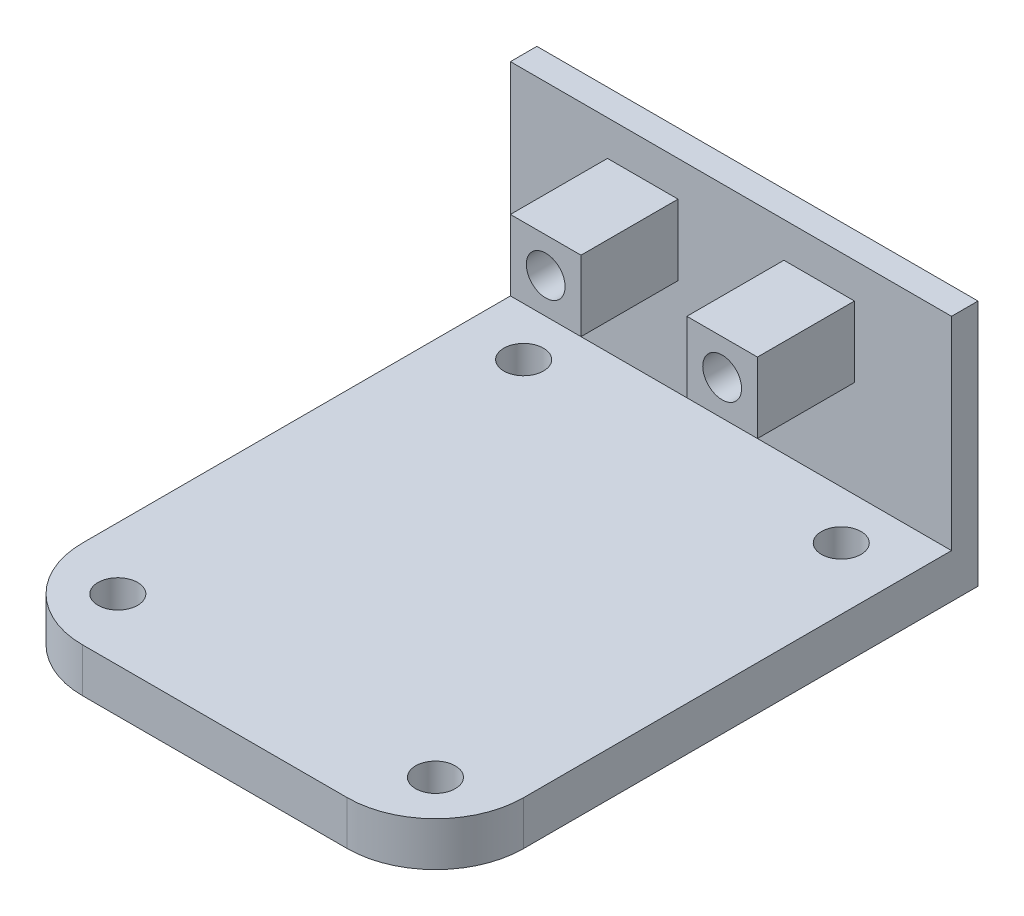
SolidWorks part; units mm, degrees
ref_plane "Front Plane" through (0, 0, 0) normal (0, 0, 1) x (1, 0, 0)
ref_plane "Top Plane" through (0, 0, 0) normal (0, 1, 0) x (1, 0, 0)
ref_plane "Right Plane" through (0, 0, 0) normal (1, 0, 0) x (0, 0, -1)
sketch "Sketch1" plane through (0, 0, 0) normal (0, 0, 1) x (1, 0, 0)
  line L1 (-25, 16.5) -> (25, 16.5)
  line L2 (-25, 16.5) -> (-25, -16.5)
  line L3 (-25, -16.5) -> (25, -16.5)
  line L4 (25, 16.5) -> (25, -16.5)
  line L5 (-25, 16.5) -> (25, -16.5) construction
  line L6 (-25, -16.5) -> (25, 16.5) construction
  point P0 (0, 0)
  dimension "D1" = 33
  dimension "D2" = 50
extrude "Boss-Extrude1" add sketch "Sketch1" along normal blind 3 contours L2 L3 L4 L1
sketch "Sketch2" plane through (0, 0, 3) normal (0, 0, 1) x (1, 0, 0)
  line L0 (25, 16.5) -> (25, -16.5) construction
  line L1 (-25, -16.5) -> (25, -16.5)
  line L2 (-25, -16.5) -> (-25, -11.5)
  line L3 (-25, -11.5) -> (25, -11.5)
  line L4 (25, -16.5) -> (25, -11.5)
  dimension "D1" = 5
extrude "Boss-Extrude2" add sketch "Sketch2" along normal blind 58.5
sketch "Sketch3" plane through (0, -11.5, 0) normal (0, 1, 0) x (1, 0, 0)
  line L0 (-25, -51.5) -> (-25, -61.5)
  line L1 (-25, -61.5) -> (-15, -61.5)
  line L2 (15, -61.5) -> (25, -61.5)
  line L3 (25, -61.5) -> (25, -51.5)
  arc A1 (15, -61.5) -> (25, -51.5) centre (15, -51.5) ccw construction
  arc A2 (15, -61.5) -> (25, -51.5) centre (15, -51.5) ccw
  arc A3 (-25, -51.5) -> (-15, -61.5) centre (-15, -51.5) ccw construction
  arc A4 (-25, -51.5) -> (-15, -61.5) centre (-15, -51.5) ccw
  circle A5 centre (-18, -54.5) radius 2.2479 construction
  circle A6 centre (-18, -54.5) radius 2.2479
  circle A7 centre (18, -54.5) radius 2.2479 construction
  circle A8 centre (18, -54.5) radius 2.2479
  circle A9 centre (-18, -8.5) radius 2.2479 construction
  circle A10 centre (-18, -8.5) radius 2.2479
  circle A11 centre (18, -8.5) radius 2.2479 construction
  circle A12 centre (18, -8.5) radius 2.2479
extrude "Cut-Extrude1" cut sketch "Sketch3" against normal up to surface (5 mm away) up to face at (0, -16.5, 30.75)
sketch "Sketch4" plane through (0, 0, 3) normal (0, 0, 1) x (1, 0, 0)
  line L5 (-14, 7.5) -> (-6, 7.5)
  line L6 (-14, 7.5) -> (-14, -0.5)
  line L7 (-14, -0.5) -> (-6, -0.5)
  line L8 (-6, 7.5) -> (-6, -0.5)
  line L9 (-14, 7.5) -> (-6, -0.5) construction
  line L10 (-14, -0.5) -> (-6, 7.5) construction
  line L11 (6, 7.5) -> (14, 7.5)
  line L12 (6, 7.5) -> (6, -0.5)
  line L13 (6, -0.5) -> (14, -0.5)
  line L14 (14, 7.5) -> (14, -0.5)
  line L15 (6, 7.5) -> (14, -0.5) construction
  line L16 (6, -0.5) -> (14, 7.5) construction
  circle A0 centre (-10, 3.5) radius 2.2 construction
  circle A1 centre (-10, 3.5) radius 2.2
  circle A2 centre (10, 3.5) radius 2.2 construction
  circle A3 centre (10, 3.5) radius 2.2
  dimension "D1" = 8
extrude "Boss-Extrude3" add sketch "Sketch4" along normal blind 11
sketch "Sketch5" plane through (0, 0, 14) normal (0, 0, 1) x (1, 0, 0)
  circle A0 centre (10, 3.5) radius 2.2 construction
  circle A1 centre (10, 3.5) radius 2.2
  circle A2 centre (-10, 3.5) radius 2.2 construction
  circle A3 centre (-10, 3.5) radius 2.2
extrude "Cut-Extrude2" cut sketch "Sketch5" against normal up to surface (14 mm away) up to face at (0, 0, 0)
sketch "Sketch6" plane through (0, 0, 3) normal (0, 0, 1) x (1, 0, 0)
  line L0 (25, 16.5) -> (25, -11.5) construction
  line L1 (-25, 16.5) -> (25, 16.5)
  line L2 (-25, 16.5) -> (-25, 11.5)
  line L3 (-25, 11.5) -> (25, 11.5)
  line L4 (25, 16.5) -> (25, 11.5)
  dimension "D1" = 5
extrude "Cut-Extrude3" cut sketch "Sketch6" against normal up to surface (3 mm away) up to face at (7.8, 3.5, 0)
